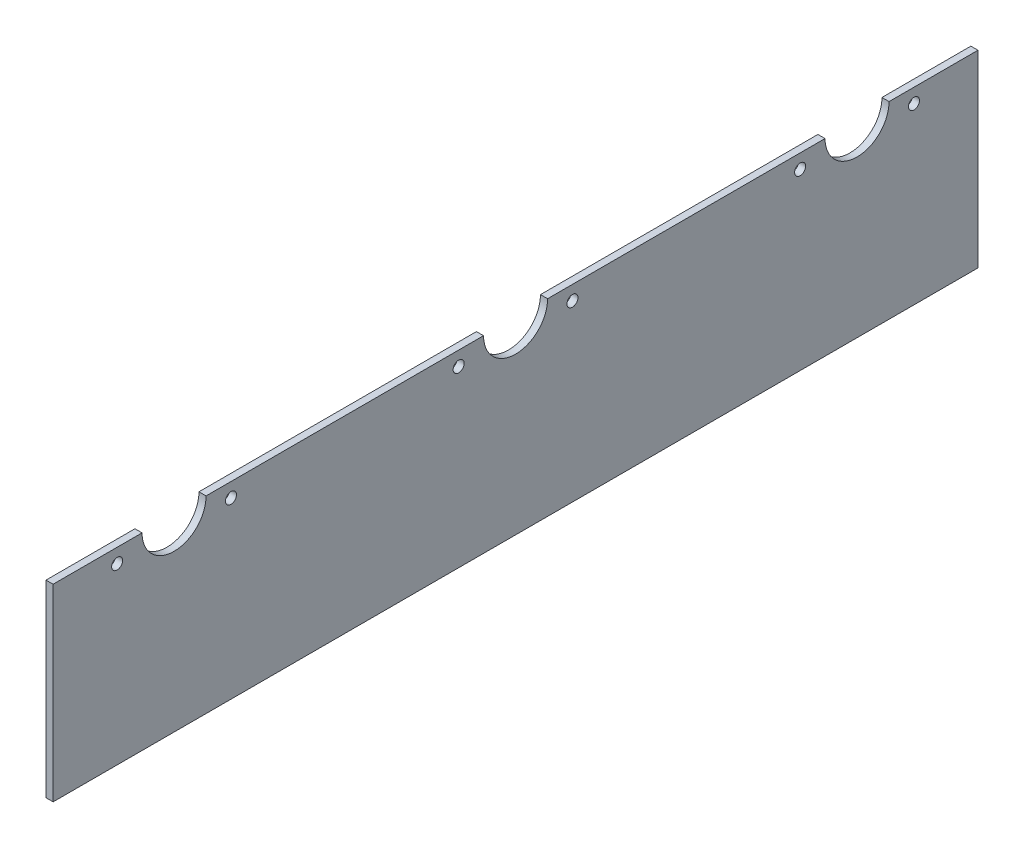
SolidWorks part; units mm, degrees
material "6061 Alloy"
ref_plane "Front Plane" through (0, 0, 0) normal (0, 0, 1) x (1, 0, 0)
ref_plane "Top Plane" through (0, 0, 0) normal (0, 1, 0) x (1, 0, 0)
ref_plane "Right Plane" through (0, 0, 0) normal (1, 0, 0) x (0, 0, -1)
sketch "Sketch1" plane through (0, 0, 0) normal (1, 0, 0) x (0, 0, -1)
  line L0 (206.375, 0) -> (-206.375, 0)
  line L1 (-206.375, 0) -> (-206.375, 84.1375)
  line L2 (-206.375, 84.1375) -> (-166.6875, 84.1375)
  line L3 (-138.1125, 84.1375) -> (-14.2875, 84.1375)
  line L4 (14.2875, 84.1375) -> (138.1125, 84.1375)
  line L5 (166.6875, 84.1375) -> (206.375, 84.1375)
  line L6 (206.375, 84.1375) -> (206.375, 0)
  line L7 (-206.375, 25.4) -> (206.375, 25.4) construction
  arc A6 (-166.6875, 84.1375) -> (-138.1125, 84.1375) centre (-152.4, 84.1375) ccw
  arc A7 (-14.2875, 84.1375) -> (14.2875, 84.1375) centre (0, 84.1375) ccw
  arc A8 (138.1125, 84.1375) -> (166.6875, 84.1375) centre (152.4, 84.1375) ccw
  point P4 (0, 0)
  dimension "D1" = 25.4
  dimension "D5" = 28.575
  dimension "D6" = 44.45
  dimension "D2" = 412.75
  dimension "D4" = 152.4
extrude "Boss-Extrude1" add sketch "Sketch1" along normal blind 3.175
hole_wizard "#10 (0.1935) Diameter Hole1" positions "Sketch2" profile "Sketch3" hole size "#10" standard "ANSI Inch" end condition through all
sketch "Sketch2" plane through (3.175, 0, 0) normal (1, 0, 0) x (0, 0, -1)
  line L0 (-177.8, 77.7875) -> (-127, 77.7875) construction
  line L2 (-25.4, 77.7875) -> (25.4, 77.7875) construction
  line L4 (127, 77.7875) -> (177.8, 77.7875) construction
  line L6 (-166.6875, 84.1375) -> (-206.375, 84.1375) construction
  line L7 (-152.4, 77.7875) -> (-152.4, 84.1375) construction
  line L9 (0, 84.1375) -> (0, 77.7875) construction
  line L11 (152.4, 84.1375) -> (152.4, 77.7875) construction
  point P0 (-177.8, 77.7875)
  point P2 (-127, 77.7875)
  point P4 (-25.4, 77.7875)
  point P6 (25.4, 77.7875)
  point P8 (127, 77.7875)
  point P10 (177.8, 77.7875)
  dimension "D1" = 50.8
  dimension "D2" = 6.35
sketch "Sketch3" plane through (3.175, 77.7875, 177.8) normal (0, 1, 0) x (0, 0, -1)
  line L0 (0, 0) -> (0, 3.175)
  line L1 (0, 3.175) -> (2.4574, 3.175)
  line L2 (2.4574, 3.175) -> (2.4574, 0)
  line L5 (2.4574, 0) -> (0, 0)
  line L11 (0, -6.35) -> (0, 107.95) construction
  dimension "Thru Hole Dia." = 4.9149
  dimension "Thru Hole Depth" = 3.175
